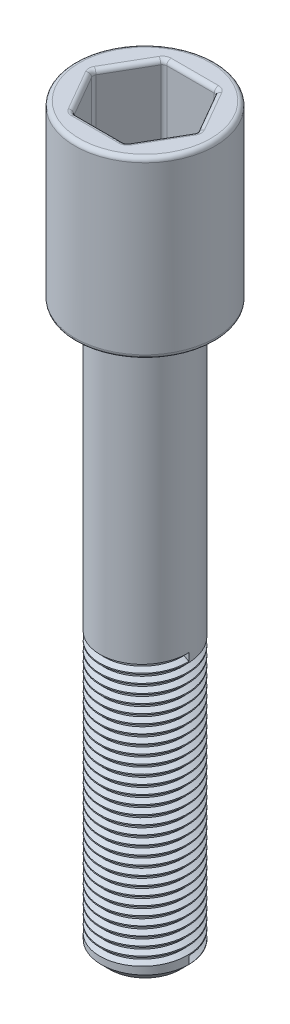
SolidWorks part; units mm, degrees
material "AISI 4140 Steel, quenched & tempered"
ref_plane "Front Plane" through (0, 0, 0) normal (1, 0, 0) x (0, 1, 0)
ref_plane "Top Plane" through (0, 0, 0) normal (0, 0, 1) x (0, 1, 0)
ref_plane "Right Plane" through (0, 0, 0) normal (0, 1, 0) x (-1, 0, 0)
sketch "Sketch1" plane through (0, 0, 0) normal (1, 0, 0) x (0, 1, 0)
  line L0 (-122.9929, 0) -> (42.9358, 0) construction
  line L1 (0, 23.268) -> (0, -20.4189) construction
  line L2 (10, 0) -> (10, 4)
  line L3 (10, 4) -> (0, 4)
  line L4 (0, 4) -> (0, 2.5)
  line L5 (0, 2.5) -> (-32, 2.5)
  line L6 (-32, 2.5) -> (-32, 0)
  line L7 (-32, 0) -> (10, 0)
  dimension "D1" = 10
  dimension "D2" = 8
  dimension "D3" = 5
  dimension "D4" = 32
revolve "Revolve1" add sketch "Sketch1" angle 360 about L0
sketch "Sketch2" plane through (0, 10, 0) normal (0, 1, 0) x (-1, 0, 0)
  line L1 (1.5, -2.5981) -> (3, 0)
  line L2 (3, 0) -> (1.5, 2.5981)
  line L3 (1.5, 2.5981) -> (-1.5, 2.5981)
  line L4 (-1.5, 2.5981) -> (-3, 0)
  line L5 (-3, 0) -> (-1.5, -2.5981)
  line L6 (-1.5, -2.5981) -> (1.5, -2.5981)
  circle A0 centre (0, 0) radius 2.5981 construction
  dimension "D1" = 3
extrude "Cut-Extrude1" cut sketch "Sketch2" against normal blind 8
ref_axis "Axis1" through (0, 16, 0) along (0, -1, 0)
thread "Thread2" pitch 0.5 method cut profile "Thread Profile2" start angle 0, offset 0.5, length 15, pitch 0.5, diameter 5
ref_plane "Plane2" through (2.5, -31.5, 0) normal (0, 0, 1) x (1, 0, 0)
sketch "Thread Profile2" plane through (2.5, -31.5, 0) normal (0, 0, 1) x (1, 0, 0)
  line L0 (0, 0) -> (0, 0.5) construction
  line L11 (0, 0) -> (0, 0.4375)
  line L12 (0, 0.4375) -> (-0.2706, 0.2812)
  line L13 (-0.2706, 0.2812) -> (-0.2706, 0.1562)
  line L15 (-0.2706, 0.1562) -> (0, 0)
  line L17 (-0.2706, 0.2187) -> (0, 0.2187) construction
  point P2 (0, 0)
  dimension "Pitch" = 0.5
  dimension "Profile_Angle" = 60
  dimension "Profile_Land" = 0.125
  dimension "Profile_Height" = 0.2706
chamfer "Chamfer1" distance 0.5 angle 45 1 edges at (0, -32, -2.5)
fillet "Fillet1" radius 0.25 20 edges at (0, 0, -4) (0, 10, -4) (0, 10, -2.5981) (-2.25, 10, -1.299) (-2.25, 10, 1.299) (0, 10, 2.5981) (2.25, 10, 1.299) (2.25, 10, -1.299) (0, 2, -2.5981) (-2.25, 2, -1.299) (-2.25, 2, 1.299) (0, 2, 2.5981) (2.25, 2, 1.299) (2.25, 2, -1.299) (-1.5, 6, -2.5981) (-1.5, 6, 2.5981) (1.5, 6, 2.5981) (3, 6, 0) (1.5, 6, -2.5981) (-3, 6, 0)
